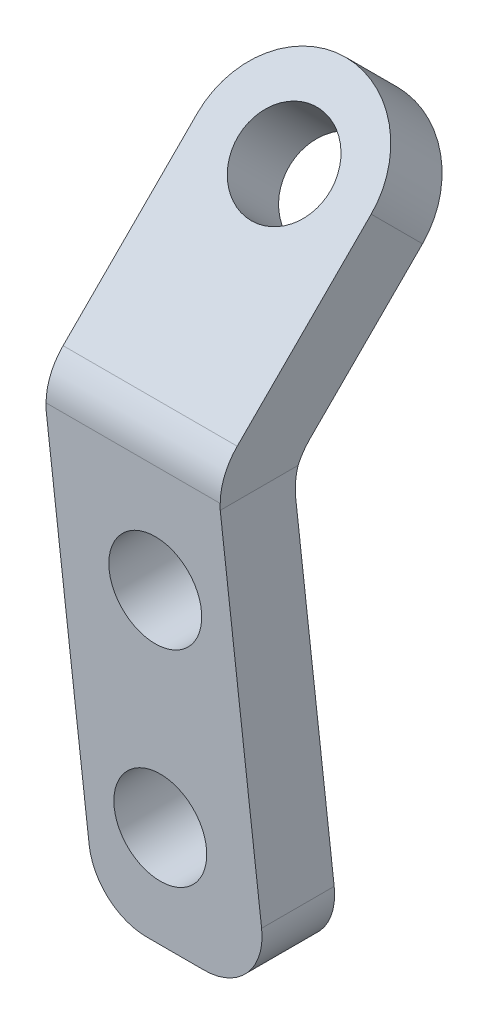
SolidWorks part; units mm, degrees
material "ABS"
ref_plane "正面" through (0, 0, 0) normal (0, 0, 1) x (1, 0, 0)
ref_plane "平面" through (0, 0, 0) normal (0, 1, 0) x (1, 0, 0)
ref_plane "右側面" through (0, 0, 0) normal (1, 0, 0) x (0, 0, -1)
ref_axis "軸1" through (-88.99, 0, 0) along (1, 0, 0)
ref_plane "平面1" through (0, 0, 0) normal (0, -0.7071, 0.7071) x (1, 0, 0)
sketch "ｽｹｯﾁ1" plane through (0, 0, 0) normal (0, -0.7071, 0.7071) x (1, 0, 0)
  line L0 (-22.697, 15) -> (-18.5, 15)
  line L3 (-18.5, 15) -> (-18.5, -15)
  line L6 (-18.5, -15) -> (-22.697, -15)
  line L7 (-18.5, 25) -> (-18.5, -25) construction
  line L8 (-25, 0) -> (-18.5, 0) construction
  line L9 (-88.99, 0) -> (88.99, 0) construction
  arc A0 (-22.697, 15) -> (-22.697, -15) centre (25, 0) ccw
  dimension "D4" = 50
  dimension "D1" = 30
  dimension "D6" = 6.5
  dimension "D7" = 25
revolve "回転1" add sketch "ｽｹｯﾁ1" angle 360 about L7
ref_axis "軸3" through (0, 0, -22.9795) along (0, 0, 1)
sketch "ｽｹｯﾁ4" plane through (0, -10.6066, -10.6066) normal (0, -0.7071, -0.7071) x (1, 0, 0)
  circle A0 centre (-18.5, 0) radius 4.197
  circle A1 centre (-18.5, 0) radius 4.197 construction
extrude "ﾎﾞｽ - 押し出し3" add sketch "ｽｹｯﾁ4" along normal blind 0.6
sketch "ｽｹｯﾁ5" plane through (0, 10.6066, 10.6066) normal (0, 0.7071, 0.7071) x (1, 0, 0)
  circle A0 centre (-18.5, 0) radius 4.197
  circle A1 centre (-18.5, 0) radius 4.197 construction
extrude "ﾎﾞｽ - 押し出し4" add sketch "ｽｹｯﾁ5" along normal blind 0.6 contours A0
sketch "ｽｹｯﾁ8" plane through (0, 11.0309, 11.0309) normal (0, 0.7071, 0.7071) x (1, 0, 0)
  line L0 (-18.5, 14.8309) -> (-18.5, -8.6872) construction
  line L2 (-15.5, -10) -> (-21.5, -10)
  line L3 (-15.5, -10) -> (-15.5, 0)
  line L4 (-15.5, 0) -> (-21.5, 0) construction
  line L5 (-21.5, -10) -> (-21.5, 0)
  line L6 (-15.5, -10) -> (-21.5, 0) construction
  line L7 (-15.5, 0) -> (-21.5, -10) construction
  circle A0 centre (-18.5, 0) radius 1.6
  arc A1 (-21.5, 0) -> (-15.5, 0) centre (-18.5, 0) cw
  point P4 (-18.5, -5)
  dimension "D1" = 3.2
  dimension "D2" = 3
  dimension "D3" = 6
  dimension "D4" = 10
extrude "ﾎﾞｽ - 押し出し6" add sketch "ｽｹｯﾁ8" along normal blind 2.5
ref_plane "平面2" through (0, 0, 18) normal (0, 0, 1) x (1, 0, 0)
sketch "ｽｹｯﾁ9" plane through (0, 0, 18) normal (0, 0, 1) x (1, 0, 0)
  circle A0 centre (0, 0) radius 27.5
  dimension "D1" = 55
extrude "ﾎﾞｽ - 押し出し7" add sketch "ｽｹｯﾁ9" against normal blind 2.5
sketch "ｽｹｯﾁ10" plane through (0, 0, 15.5) normal (0, 0, -1) x (-1, 0, 0)
  line L1 (27.5, -9.9027) -> (21.5, -9.9027)
  line L2 (27.5, -9.9027) -> (27.5, 10.0973)
  line L3 (27.5, 10.0973) -> (21.5, 10.0973)
  line L4 (21.5, -9.9027) -> (21.5, 10.0973)
  line L5 (27.5, -9.9027) -> (21.5, 10.0973) construction
  line L6 (27.5, 10.0973) -> (21.5, -9.9027) construction
  circle A1 centre (0, 0) radius 27.5 construction
  point P0 (24.5, 0.0973)
  dimension "D1" = 20
extrude "ｶｯﾄ - 押し出し1" cut sketch "ｽｹｯﾁ10" against normal through all
sketch "ｽｹｯﾁ16" plane through (0, 0, 15.5) normal (0, 0, -1) x (-1, 0, 0)
  line L0 (25.5792, 10.0973) -> (15.5, 10.0973)
  line L1 (15.5, 10.0973) -> (15.5, 22.7156)
  arc A0 (25.5792, 10.0973) -> (25.6551, -9.9027) centre (0, 0) ccw construction
  arc A1 (25.5792, 10.0973) -> (15.5, 22.7156) centre (0, 0) ccw
extrude "ｶｯﾄ - 押し出し8" cut sketch "ｽｹｯﾁ16" against normal through all
sketch "ｽｹｯﾁ17" plane through (-21.5, 0, 0) normal (-1, 0, 0) x (0, 0, 1)
  line L0 (15.5, 10.0973) -> (18, 10.0973)
  line L1 (18, 10.0973) -> (19.8697, 5.7276)
  line L2 (19.8697, 5.7276) -> (18.1019, 3.9598)
  line L3 (18.1019, 3.9598) -> (18, 4.0617)
  line L4 (18, 4.0617) -> (18, 7.5973)
  line L5 (18, 7.5973) -> (15.5, 10.0973)
extrude "ｶｯﾄ - 押し出し9" cut sketch "ｽｹｯﾁ17" against normal up to surface (6 mm away) up to face at (-15.5, 16.4064, 16.75)
sketch "ｽｹｯﾁ19" plane through (0, -11.0309, -11.0309) normal (0, -0.7071, -0.7071) x (1, 0, 0)
  circle A0 centre (-18.5, 0) radius 4.197
  circle A1 centre (-18.5, 0) radius 4.197 construction
extrude "ｶｯﾄ - 押し出し10" cut sketch "ｽｹｯﾁ19" against normal up to surface (31.2 mm away) up to face at (-18.5, 7.5355, 14.5262)
sketch "ｽｹｯﾁ20" plane through (0, 0, 15.5) normal (0, 0, -1) x (-1, 0, 0)
  line L0 (17.4777, -7.435) -> (17.8244, 6.5617) construction
  line L1 (15.5, 6.5617) -> (21.5, 6.5617) construction
  line L5 (21.5, 6.5617) -> (19.8021, -7.435)
  line L6 (19.8021, -7.435) -> (13.8021, -7.435)
  line L7 (13.8021, -7.435) -> (15.5, 6.5617)
  line L8 (15.5, 6.5617) -> (15.5, 22.7156)
  line L9 (25.6551, -9.9027) -> (21.5, -9.9027)
  line L10 (21.5, -9.9027) -> (21.5, 6.5617)
  line L11 (17.4777, -7.435) -> (21.5, 6.5617) construction
  line L12 (17.8244, 6.5617) -> (13.8021, -7.435) construction
  circle A0 centre (17.7377, 3.0617) radius 1.6
  circle A1 centre (17.5644, -3.9361) radius 1.6
  arc A4 (25.6551, -9.9027) -> (15.5, 22.7156) centre (0, 0) cw
  dimension "D1" = 3.2
  dimension "D2" = 3.5
  dimension "D3" = 7
  dimension "D4" = 3.5
  dimension "D5" = 18
  dimension "D6" = 18
extrude "ｶｯﾄ - 押し出し11" cut sketch "ｽｹｯﾁ20" against normal through all
fillet "ﾌｨﾚｯﾄ1" radius 2 4 edges at (-18.5, 7.5973, 18) (-13.8021, -7.435, 16.75) (-18.5, 6.5617, 15.5) (-19.8021, -7.435, 16.75)
